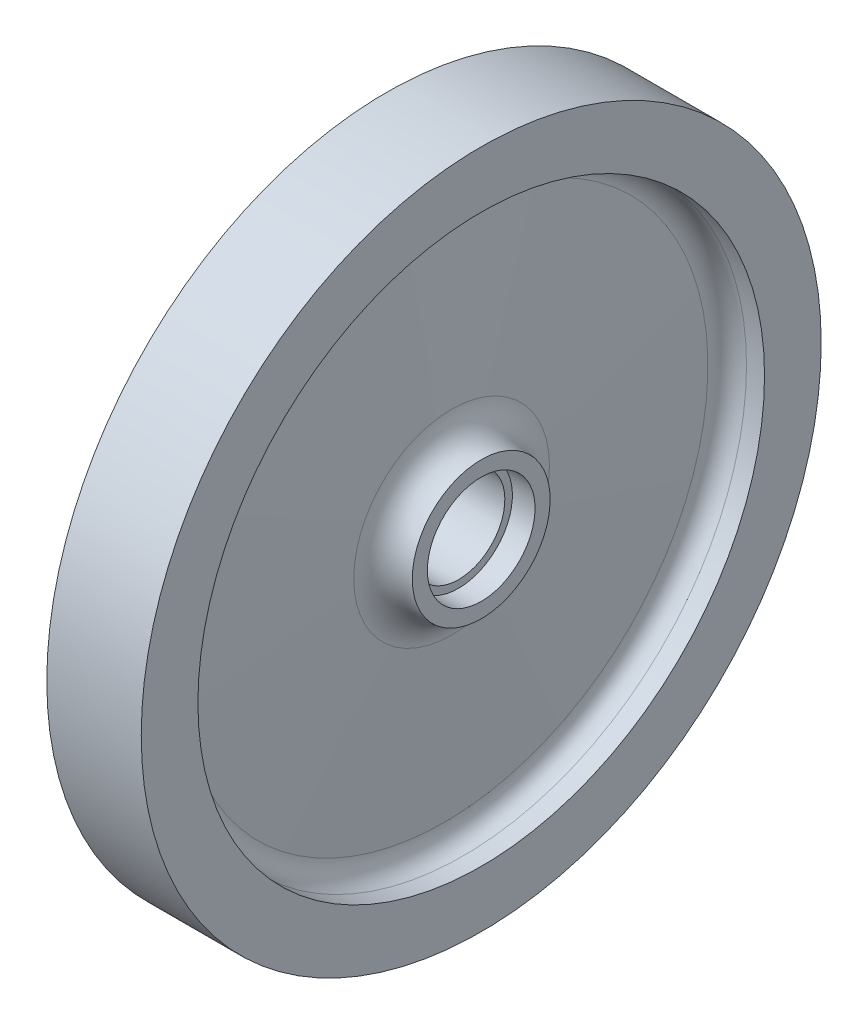
SolidWorks part; units mm, degrees
ref_plane "Front Plane" through (0, 0, 0) normal (0, 0, 1) x (1, 0, 0)
ref_plane "Top Plane" through (0, 0, 0) normal (0, 1, 0) x (1, 0, 0)
ref_plane "Right Plane" through (0, 0, 0) normal (1, 0, 0) x (0, 0, -1)
sketch "Sketch1" plane through (0, 0, 0) normal (0, 0, 1) x (1, 0, 0)
  line L0 (-2.5, 75) -> (-5, 18.25)
  line L1 (-12.5, 90) -> (12.5, 90)
  line L2 (-12.5, 90) -> (-12.5, 75)
  line L3 (-12.5, 75) -> (-2.5, 75)
  line L4 (12.5, 90) -> (12.5, 75)
  line L5 (-12.5, 90) -> (12.5, 75) construction
  line L6 (-12.5, 75) -> (12.5, 90) construction
  line L7 (2.5, 75) -> (5, 18.25)
  line L8 (-5, 18.25) -> (5, 18.25) construction
  line L9 (-2.5, 75) -> (2.5, 75) construction
  line L10 (12.5, 14.25) -> (6.5, 14.25)
  line L11 (12.5, 14.25) -> (12.5, 18.25)
  line L12 (12.5, 18.25) -> (5, 18.25)
  line L13 (-12.5, 14.25) -> (-12.5, 18.25)
  line L14 (12.5, 14.25) -> (-12.5, 18.25) construction
  line L15 (12.5, 18.25) -> (-12.5, 14.25) construction
  line L16 (-6.5, 12.25) -> (6.5, 12.25)
  line L17 (-6.5, 12.25) -> (-6.5, 14.25)
  line L18 (-6.5, 14.25) -> (6.5, 14.25) construction
  line L19 (6.5, 12.25) -> (6.5, 14.25)
  line L20 (-6.5, 12.25) -> (6.5, 14.25) construction
  line L21 (-6.5, 14.25) -> (6.5, 12.25) construction
  line L22 (2.5, 75) -> (12.5, 75)
  line L23 (5, 18.25) -> (-5, 18.25) construction
  line L24 (-5, 18.25) -> (-12.5, 18.25)
  line L25 (6.5, 14.25) -> (-6.5, 14.25) construction
  line L26 (-6.5, 14.25) -> (-12.5, 14.25)
  point P0 (0, 82.5)
  point P10 (0, 18.25)
  point P11 (0, 16.25)
  point P18 (0, 13.25)
  dimension "D1" = 90
  dimension "D2" = 25
  dimension "D3" = 15
  dimension "D4" = 5
  dimension "D5" = 10
  dimension "D6" = 18.25
  dimension "D7" = 4
  dimension "D8" = 2
  dimension "D9" = 13
ref_axis "Axis1" through (-13.75, 0, 0) along (1, 0, 0)
revolve "Revolve1" add sketch "Sketch1" angle 360 about axis through (-13.75, 0, 0) along (1, 0, 0)
fillet "Fillet1" radius 5 2 edges at (-2.5, 0, 75) (2.5, 0, 75)
fillet "Fillet2" radius 8 2 edges at (-5, 0, 18.25) (5, 0, 18.25)
sketch "Sketch4" plane through (0, 0, 0) normal (1, 0, 0) x (0, 0, -1)
  line L0 (-2.3813, 12.0163) -> (2.3813, 12.0163) construction
  line L1 (-2.3813, 12.0163) -> (-2.3813, 14.0496)
  line L2 (-2.3813, 14.0496) -> (2.3813, 14.0496)
  line L3 (2.3813, 14.0496) -> (2.3813, 12.0163)
  arc A0 (-2.3813, 12.0163) -> (2.3813, 12.0163) centre (0, 0) cw
  circle A1 centre (0, 0) radius 12.25 construction
  circle A2 centre (0, 0) radius 14.25 construction
  circle A3 centre (0, 0) radius 14.25 construction
  point P6 (0, 12.0163)
  dimension "D1" = 4.7625
extrude "Cut-Extrude1" cut sketch "Sketch4" against normal up to next and the other way up to next
equation "\"D1@Sketch1\"=18cm/2"
